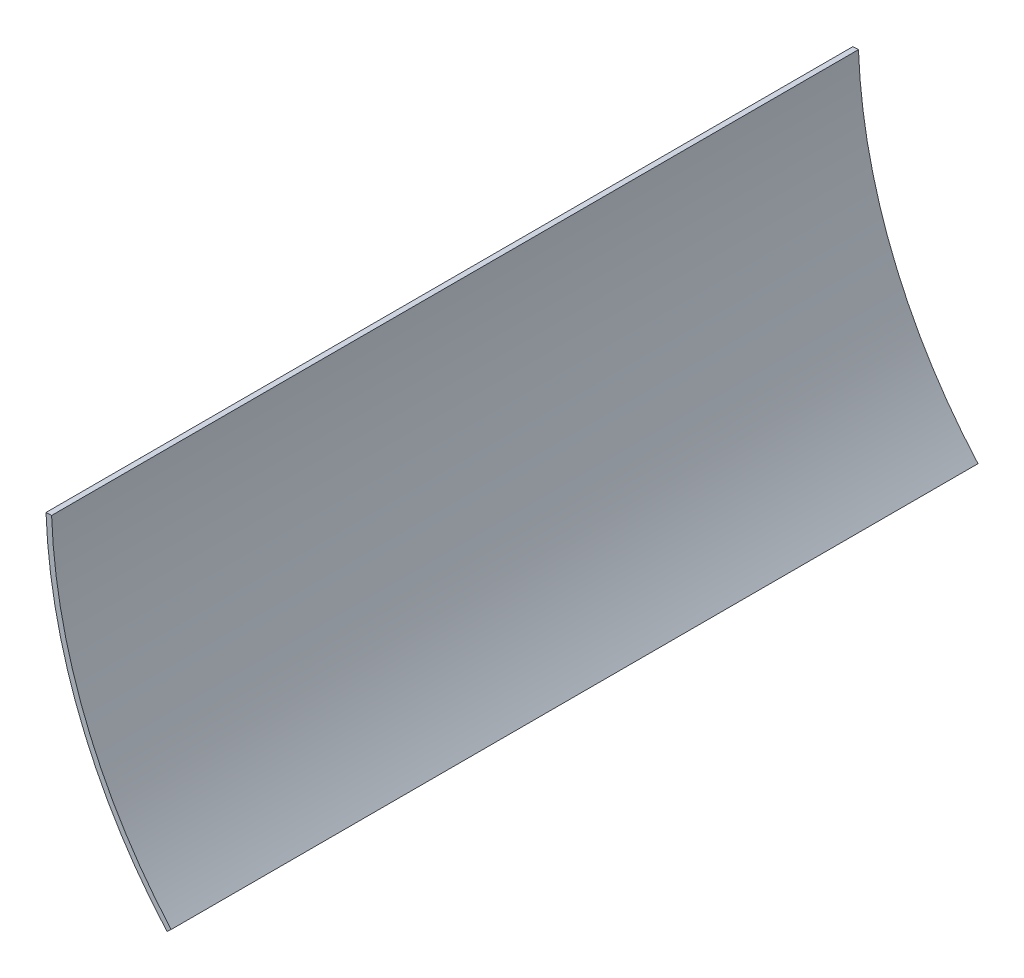
SolidWorks part; units mm, degrees
ref_plane "Front Plane" through (0, 0, 0) normal (0, 0, 1) x (1, 0, 0)
ref_plane "Top Plane" through (0, 0, 0) normal (0, 1, 0) x (1, 0, 0)
ref_plane "Right Plane" through (0, 0, 0) normal (1, 0, 0) x (0, 0, -1)
sketch "Sketch1" plane through (0, 0, 0) normal (0, 0, 1) x (1, 0, 0)
  arc A0 (0, 0) -> (101.6, -254) centre (406.1184, 15.1273) ccw
  dimension "D1" = 406.4
  dimension "D2" = 101.6
  dimension "D3" = 254
extrude "Extrude-Thin1" add sketch "Sketch1" along normal mid plane 685.8 thin thin type one direction wall 4.7625
sketch "Sketch2" plane through (0, 0, 342.9) normal (0, 0, 1) x (1, 0, 0)
  line L0 (-9.289, -72.4697) -> (4.3954, -72.4697)
  line L1 (-9.289, -97.8697) -> (10.7878, -97.8697)
  arc A1 (-9.289, -72.4697) -> (-9.289, -97.8697) centre (-9.289, -85.1697) ccw
  arc A2 (-4.7592, -0.1773) -> (98.0314, -257.1538) centre (406.1184, 15.1273) ccw construction
  circle A4 centre (-9.289, -85.1697) radius 3.175 construction
  arc A5 (4.3954, -72.4697) -> (10.7878, -97.8697) centre (406.1184, 15.1273) ccw
  dimension "D1" = 25.4
extrude "Boss-Extrude1" [suppressed] add sketch "Sketch2" against normal offset from surface (279.4 mm away) 203.2 from offset 203.2 offset against normal yes
sketch "Sketch3" [suppressed] plane through (0, 0, 139.7) normal (0, 0, 1) x (1, 0, 0)
  line L2 (-9.289, -97.8697) -> (10.7878, -97.8697)
  line L3 (4.3954, -72.4697) -> (-9.289, -72.4697)
  line L4 (-9.289, -97.8697) -> (10.7878, -97.8697)
  line L5 (4.3954, -72.4697) -> (-9.289, -72.4697)
  arc A2 (-9.289, -72.4697) -> (-9.289, -97.8697) centre (-9.289, -85.1697) ccw
  arc A3 (4.3954, -72.4697) -> (10.7878, -97.8697) centre (406.1184, 15.1273) ccw
  arc A4 (-9.289, -72.4697) -> (-9.289, -97.8697) centre (-9.289, -85.1697) ccw
  arc A5 (4.3954, -72.4697) -> (10.7878, -97.8697) centre (406.1184, 15.1273) ccw
  dimension "D1" = 0
extrude "Cut-Extrude1" [suppressed] cut sketch "Sketch3" against normal offset from surface (203.2 mm away) 38.1 from offset 38.1 offset against normal yes
sketch "Sketch4" [suppressed] plane through (0, 0, -101.6) normal (0, 0, 1) x (1, 0, 0)
  circle A0 centre (-9.289, -85.1697) radius 3.048
  arc A1 (-9.289, -72.4697) -> (-9.289, -97.8697) centre (-9.289, -85.1697) ccw construction
  circle A2 centre (-9.289, -85.1697) radius 12.7
  arc A3 (-9.289, -72.4697) -> (-9.289, -97.8697) centre (-9.289, -85.1697) ccw construction
  arc M2 (-9.289, -72.4697) -> (-9.289, -97.8697) centre (-9.289, -85.1697) ccw
  dimension "D1" = 6.096
extrude "Cut-Extrude2" [suppressed] cut sketch "Sketch4" against normal offset from surface (19.05 mm away) 9.525 from offset 9.525 contours A2 A0 M2 offset against normal yes
sketch "Sketch5" [suppressed] plane through (0, 0, 101.6) normal (0, 0, -1) x (-1, 0, 0)
  circle A0 centre (9.289, -85.1697) radius 3.048
  arc A1 (9.289, -97.8697) -> (9.289, -72.4697) centre (9.289, -85.1697) ccw construction
  circle A2 centre (9.289, -85.1697) radius 12.7
  arc M3 (9.289, -97.8697) -> (9.289, -72.4697) centre (9.289, -85.1697) ccw
  dimension "D1" = 6.096
extrude "Cut-Extrude3" [suppressed] cut sketch "Sketch5" against normal offset from surface (19.05 mm away) 9.525 from offset 9.525 contours A2 A0 M3 offset against normal yes
sketch "Sketch6" plane through (0, 0, -342.9) normal (0, 0, -1) x (-1, 0, 0)
  line L0 (-23.1889, -161.9038) -> (-35.0192, -161.9038)
  line L1 (-23.1889, -200.0038) -> (-55.7283, -200.0038)
  arc A0 (-23.1889, -200.0038) -> (-23.1889, -161.9038) centre (-23.1889, -180.9538) ccw
  arc A1 (-98.0314, -257.1538) -> (4.7592, -0.1773) centre (-406.1184, 15.1273) ccw construction
  arc A2 (-55.7283, -200.0038) -> (-35.0192, -161.9038) centre (-406.1184, 15.1273) ccw
  dimension "D1" = 38.1
  dimension "D2" = 76.2
extrude "Boss-Extrude2" [suppressed] add sketch "Sketch6" against normal up to surface (685.8 mm away)
ref_plane "Plane1" through (0, -257.1538, 0) normal (0, 1, 0) x (1, 0, 0)
sketch "Sketch8" plane through (0, -257.1538, 0) normal (0, 1, 0) x (1, 0, 0)
  line L0 (-58.4976, 0) -> (58.4976, 0) construction
  line L1 (-4.7592, -190.5) -> (101.6, -190.5) construction
  line L2 (-4.7592, -342.9) -> (-4.7592, 342.9) construction
  line L3 (101.6, -342.9) -> (101.6, 342.9) construction
  line L4 (-4.7592, -342.9) -> (98.0314, -342.9) construction
  circle A0 centre (14.2908, -190.5) radius 19.05
  circle A1 centre (14.2908, 190.5) radius 19.05
  point P12 (0, 0)
  point P13 (51.7872, -189.031)
  point P16 (15.9818, -190.5)
  point P18 (0, 0)
  dimension "D1" = 38.1
  dimension "D2" = 152.4
extrude "Boss-Extrude3" add sketch "Sketch8" along normal up to surface (147.6788 mm away) up to face at (35.4998, -133.1201, 0)
